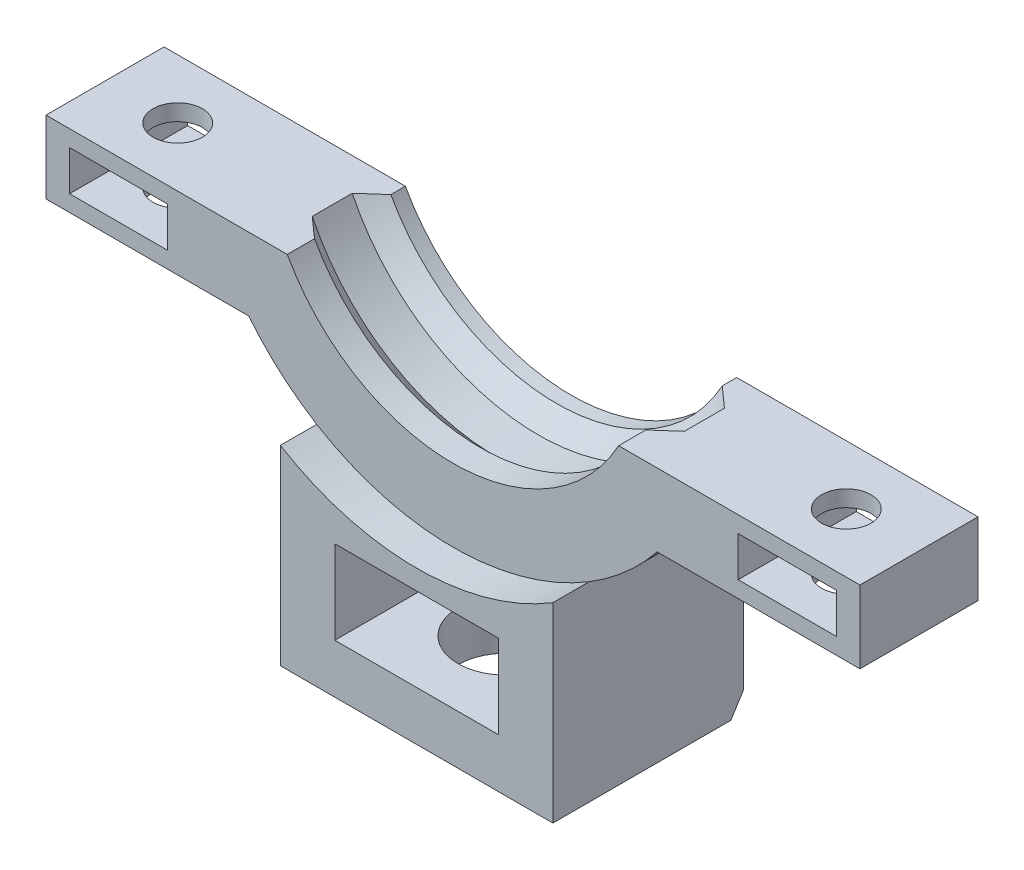
SolidWorks part; units mm, degrees
ref_plane "Front Plane" through (0, 0, 0) normal (0, 0, 1) x (1, 0, 0)
ref_plane "Top Plane" through (0, 0, 0) normal (0, 1, 0) x (1, 0, 0)
ref_plane "Right Plane" through (0, 0, 0) normal (1, 0, 0) x (0, 0, -1)
sketch "Sketch1" plane through (0, 0, 0) normal (0, 0, 1) x (1, 0, 0)
  circle A0 centre (0, 0) radius 18.288
  dimension "D1" = 36.576
extrude "Boss-Extrude1" add sketch "Sketch1" along normal blind 19.05
sketch "Sketch3" plane through (0, 0, 19.05) normal (0, 0, 1) x (1, 0, 0)
  circle A0 centre (0, 0) radius 13.208
  dimension "D2" = 26.416
extrude "Cut-Extrude1" cut sketch "Sketch3" against normal through all
ref_plane "Plane2" through (0, -13.716, 0) normal (0, 1, 0) x (1, 0, 0)
sketch "Sketch15" plane through (0, -13.716, 0) normal (0, 1, 0) x (1, 0, 0)
  line L0 (0, -19.05) -> (0, 0) construction
  line L1 (-9.525, -0.762) -> (9.525, -0.762)
  line L2 (-9.525, -0.762) -> (-9.525, -18.288)
  line L3 (-9.525, -18.288) -> (9.525, -18.288)
  line L4 (9.525, -0.762) -> (9.525, -18.288)
  line L5 (-9.525, -0.762) -> (9.525, -18.288) construction
  line L6 (-9.525, -18.288) -> (9.525, -0.762) construction
  line L7 (-13.208, -19.05) -> (13.208, -19.05) construction
  line L8 (18.288, 0) -> (-18.288, 0) construction
  point P0 (0, -9.525)
  dimension "D1" = 19.05
  dimension "D2" = 0.762
  dimension "D3" = 0.762
extrude "Boss-Extrude3" add sketch "Sketch15" against normal blind 15.24
sketch "Sketch16" plane through (0, 0, 18.288) normal (0, 0, 1) x (1, 0, 0)
  line L0 (-9.525, -28.956) -> (-9.525, -15.6117) construction
  line L1 (-5.715, -25.5076) -> (5.715, -25.5076)
  line L2 (-5.715, -25.5076) -> (-5.715, -19.6656)
  line L3 (-5.715, -19.6656) -> (5.715, -19.6656)
  line L4 (5.715, -25.5076) -> (5.715, -19.6656)
  line L5 (-5.715, -25.5076) -> (5.715, -19.6656) construction
  line L6 (-5.715, -19.6656) -> (5.715, -25.5076) construction
  point P0 (0, -22.5866)
  dimension "D1" = 5.842
  dimension "D2" = 11.43
  dimension "D3" = 3.81
extrude "Cut-Extrude4" cut sketch "Sketch16" against normal through all
chamfer "Chamfer1" distance 5.08 angle 58 1 edges at (0, -28.956, 0.762) first distance on face at (0, -28.956, 9.525)
hole_wizard "1/4 Clearance Hole1" positions "Sketch18" profile "Sketch17" hole size "1/4" standard "ANSI Inch" end condition up to next
sketch "Sketch18" plane through (0, -28.956, 0) normal (0, -1, 0) x (-1, 0, 0)
  line L0 (0, -18.288) -> (0, -0.762) construction
  point P0 (0, -12.0214)
sketch "Sketch17" plane through (0, -28.956, 12.0214) normal (1, 0, 0) x (0, 0, -1)
  line L0 (0, 0) -> (0, 3.4484)
  line L1 (0, 3.4484) -> (3.3782, 3.4484)
  line L2 (3.3782, 3.4484) -> (3.3782, 0)
  line L5 (3.3782, 0) -> (0, 0)
  line L11 (0, -6.35) -> (0, 107.95) construction
  dimension "Thru Hole Dia." = 6.7564
  dimension "Thru Hole Depth" = 3.4484
sketch "Sketch19" plane through (0, 0, 19.05) normal (0, 0, 1) x (1, 0, 0)
  circle A0 centre (0, 0) radius 18.288
  circle A1 centre (0, 0) radius 13.208
extrude "Cut-Extrude5" cut sketch "Sketch19" against normal up to surface (0.762 mm away) up to face at (0, -22.5866, 18.288)
sketch "Sketch20" plane through (0, 0, 18.288) normal (0, 0, 1) x (1, 0, 0)
  circle A0 centre (0, 0) radius 18.288
extrude "Cut-Extrude6" cut sketch "Sketch20" against normal blind 2.54
sketch "Sketch21" plane through (0, 0, 0) normal (0, 0, -1) x (-1, 0, 0)
  circle A0 centre (0, 0) radius 18.288
extrude "Cut-Extrude7" cut sketch "Sketch21" against normal offset from surface (7.493 mm away) 8.255 up to face at (0, 0, 15.748)
sketch "Sketch22" plane through (0, -13.716, 0) normal (0, 1, 0) x (1, 0, 0)
  line L0 (9.525, -7.493) -> (9.525, -0.762) construction
  line L1 (-9.525, -0.762) -> (9.525, -0.762)
  line L2 (-9.525, -0.762) -> (-9.525, -4.953)
  line L3 (-9.525, -4.953) -> (9.525, -4.953)
  line L4 (9.525, -0.762) -> (9.525, -4.953)
  line L5 (18.288, -7.493) -> (-18.288, -7.493) construction
  dimension "D1" = 2.54
extrude "Cut-Extrude8" cut sketch "Sketch22" against normal through all
ref_plane "Plane3" through (0, 0, 13.843) normal (0, 0, 1) x (1, 0, 0)
sketch "Sketch24" plane through (0, 0, 13.843) normal (0, 0, 1) x (1, 0, 0)
  circle A0 centre (0, 0) radius 14.478
  circle A1 centre (0, 0) radius 13.208 construction
  dimension "D1" = 1.27
extrude "Cut-Extrude10" cut sketch "Sketch24" against normal blind 5.334
ref_plane "Plane4" through (0, -6.35, 0) normal (0, 1, 0) x (1, 0, 0)
ref_plane "Plane5" through (0, 6.35, 0) normal (0, 1, 0) x (1, 0, 0)
ref_plane "Plane6" through (13.208, 0, 0) normal (1, 0, 0) x (0, 0, -1)
sketch "Sketch25" plane through (13.208, 0, 0) normal (1, 0, 0) x (0, 0, -1)
  line L0 (-15.748, 18.288) -> (-15.748, -15.6117) construction
  line L1 (-15.748, 11.43) -> (-7.493, 11.43)
  line L2 (-15.748, 11.43) -> (-15.748, 6.35)
  line L3 (-15.748, 6.35) -> (-7.493, 6.35)
  line L4 (-7.493, 11.43) -> (-7.493, 6.35)
  line L5 (7.3343, 6.35) -> (-7.3343, 6.35) construction
  line L6 (-7.493, -15.6117) -> (-7.493, 18.288) construction
  line L7 (7.3343, -6.35) -> (-7.3343, -6.35) construction
  line L8 (-15.748, -11.43) -> (-7.493, -11.43)
  line L9 (-15.748, -11.43) -> (-15.748, -6.35)
  line L10 (-15.748, -6.35) -> (-7.493, -6.35)
  line L11 (-7.493, -11.43) -> (-7.493, -6.35)
  dimension "D1" = 5.08
  dimension "D2" = 5.08
extrude "Boss-Extrude4" add sketch "Sketch25" along normal blind 15.24
hole_wizard "#4 Clearance Hole1" positions "Sketch27" profile "Sketch26" hole size "#4" standard "ANSI Inch" end condition through all
sketch "Sketch27" plane through (0, -11.43, 0) normal (0, -1, 0) x (-1, 0, 0)
  line L0 (-28.448, -15.748) -> (-14.2761, -15.748) construction
  line L1 (-28.448, -15.748) -> (-28.448, -7.493) construction
  line L2 (-14.2761, -15.748) -> (-14.2761, -7.493) construction
  point P0 (-23.368, -11.6205)
  dimension "D1" = 4.1275
  dimension "D2" = 5.08
  dimension "D3" = 9.0919
sketch "Sketch26" plane through (23.368, -11.43, 11.6205) normal (1, 0, 0) x (0, 0, -1)
  line L0 (0, 0) -> (0, 29.718)
  line L1 (0, 29.718) -> (1.7272, 29.718)
  line L2 (1.7272, 29.718) -> (1.7272, 0)
  line L5 (1.7272, 0) -> (0, 0)
  line L11 (0, -6.35) -> (0, 107.95) construction
  dimension "Thru Hole Dia." = 3.4544
  dimension "Thru Hole Depth" = 29.718
sketch "Sketch28" plane through (0, 0, 15.748) normal (0, 0, 1) x (1, 0, 0)
  line L0 (23.368, -6.35) -> (23.368, -11.43) construction
  line L1 (19.939, -10.287) -> (26.797, -10.287)
  line L2 (19.939, -10.287) -> (19.939, -7.493)
  line L3 (19.939, -7.493) -> (26.797, -7.493)
  line L4 (26.797, -10.287) -> (26.797, -7.493)
  line L5 (19.939, -10.287) -> (26.797, -7.493) construction
  line L6 (19.939, -7.493) -> (26.797, -10.287) construction
  line L7 (7.3343, -6.35) -> (-7.3343, -6.35) construction
  point P0 (23.368, -8.89)
  dimension "D1" = 2.794
  dimension "D2" = 6.858
  dimension "D3" = 1.143
extrude "Cut-Extrude11" cut sketch "Sketch28" against normal through all
mirror "Mirror2" about plane through (0, 0, 0) normal (0, 1, 0) of "Cut-Extrude11"
mirror "Mirror3" about plane through (0, 0, 0) normal (1, 0, 0) of "Mirror2", "Cut-Extrude11", "#4 Clearance Hole1", "Boss-Extrude4"
ref_plane "Plane7" through (0, 18.288, 0) normal (0, 1, 0) x (1, 0, 0)
sketch "Sketch30" plane through (0, 18.288, 0) normal (0, 1, 0) x (1, 0, 0)
  line L1 (-34.7196, 0) -> (34.9258, 0)
  line L2 (-34.7196, 0) -> (-34.7196, -31.0085)
  line L3 (-34.7196, -31.0085) -> (34.9258, -31.0085)
  line L4 (34.9258, 0) -> (34.9258, -31.0085)
extrude "Cut-Extrude13" cut sketch "Sketch30" against normal up to surface (24.638 mm away) up to face at (23.368, -6.35, 9.8933)
chamfer "Chamfer2" distance 1.27 angle 45 2 edges at (0, -14.478, 13.843) (0, -14.478, 8.509)
